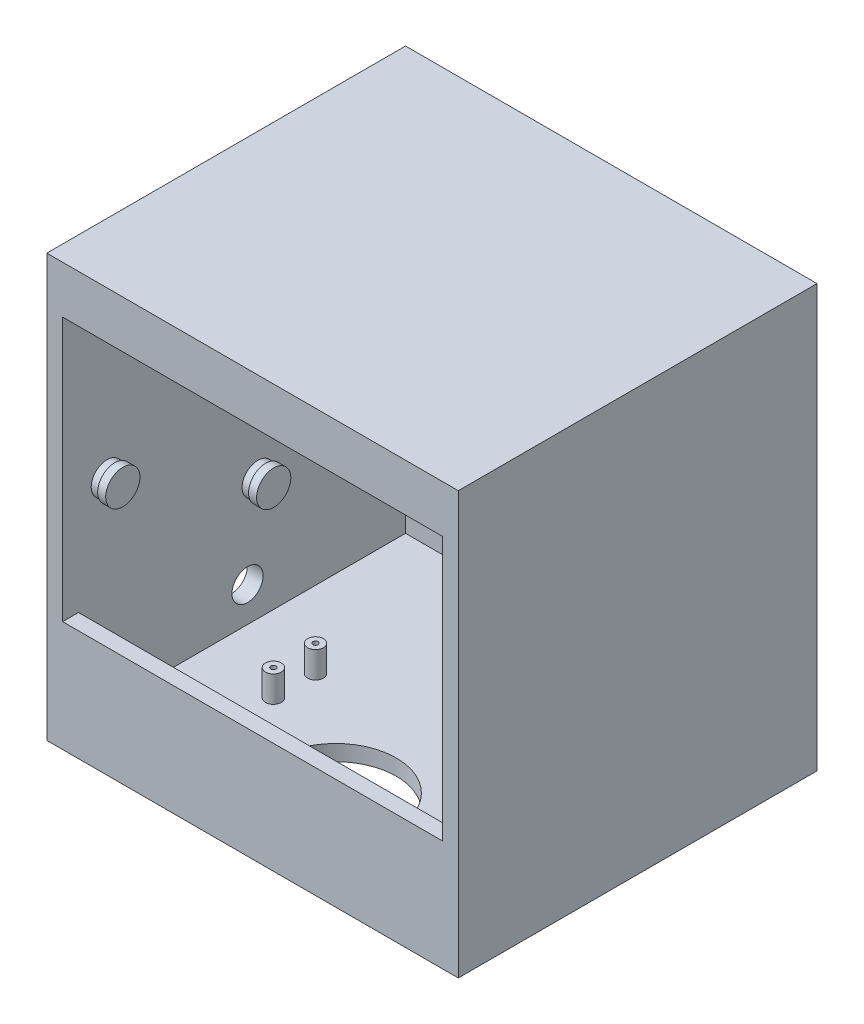
SolidWorks part; units mm, degrees
ref_plane "Front Plane" through (0, 0, 0) normal (0, 0, 1) x (1, 0, 0)
ref_plane "Top Plane" through (0, 0, 0) normal (0, 1, 0) x (1, 0, 0)
ref_plane "Right Plane" through (0, 0, 0) normal (1, 0, 0) x (0, 0, -1)
sketch "Base Plate Sketch" plane through (0, 0, 0) normal (0, 1, 0) x (1, 0, 0)
  line L1 (-176.9042, 232.645) -> (280.2958, 232.645)
  line L2 (-176.9042, 232.645) -> (-176.9042, -161.055)
  line L3 (-176.9042, -161.055) -> (280.2958, -161.055)
  line L4 (280.2958, 232.645) -> (280.2958, -161.055)
  line L5 (-195.9542, 251.695) -> (299.3458, 251.695)
  line L6 (-195.9542, 251.695) -> (-195.9542, -180.105)
  line L7 (-195.9542, -180.105) -> (299.3458, -180.105)
  line L8 (299.3458, 251.695) -> (299.3458, -180.105)
  line L9 (51.6958, 232.645) -> (51.6958, -161.055)
  circle A0 centre (51.6958, -80.0925) radius 73.025
  circle A1 centre (-72.1292, -80.755) radius 4.1
  circle A2 centre (-72.1292, 203.67) radius 4.1
  circle A3 centre (-84.8292, 32.22) radius 9.5
  circle A4 centre (-84.8292, -18.5299) radius 9.5
  circle A5 centre (-84.8292, 32.22) radius 3.175
  circle A6 centre (-84.8292, -18.5299) radius 3.175
  circle A7 centre (175.5208, -80.755) radius 4.1
  circle A8 centre (188.2208, -18.5299) radius 3.175
  circle A9 centre (188.2208, -18.5299) radius 9.5
  circle A10 centre (188.2208, 32.22) radius 3.175
  circle A11 centre (188.2208, 32.22) radius 9.5
  circle A12 centre (175.5208, 203.67) radius 4.1
  dimension "D7" = 146.05
  dimension "D9" = 8.2
  dimension "D10" = 12.7
  dimension "D11" = 80.3
  dimension "D12" = 8.2
  dimension "D13" = 284.425
  dimension "D14" = 19
  dimension "D15" = 19
  dimension "D19" = 6.35
  dimension "D20" = 6.35
  dimension "D1" = 393.7
  dimension "D2" = 457.2
  dimension "D3" = 19.05
  dimension "D4" = 19.05
  dimension "D5" = 19.05
  dimension "D6" = 19.05
  dimension "D8" = 312.7375
  dimension "D16" = 50.75
  dimension "D17" = 123.825
  dimension "D21" = 28.975
  dimension "D22" = 171.45
extrude "Boss-Extrude2" add sketch "Base Plate Sketch" along normal blind 31.75 contours A10 | A11 | A8 | A9 | A5 | A3 | A6 | A4
extrude "Boss-Extrude3" add sketch "Sketch1<5>" against normal blind 19.05 contours L5 L8 L7 L6
sketch "Sketch1<5>" plane through (0, 0, 0) normal (0, 1, 0) x (1, 0, 0) same geometry as "Base Plate Sketch"
extrude "Cut-Extrude1" cut sketch "Sketch1<6>" against normal blind 99.05 contours A2 | A1 | A0 | A7 | A12
sketch "Sketch1<6>" plane through (0, 0, 0) normal (0, 1, 0) x (1, 0, 0) same geometry as "Base Plate Sketch"
extrude "Boss-Extrude4" add sketch "Sketch1<7>" along normal blind 469.9 contours L6 L7 L8 L5 | L2 L3 L4 L1
sketch "Sketch1<7>" plane through (0, 0, 0) normal (0, 1, 0) x (1, 0, 0) same geometry as "Base Plate Sketch"
ref_plane "Plane1" through (-176.9042, 0, -232.645) normal (1, 0, 0) x (0, 0, -1)
sketch "Back Wall Sketch" plane through (0, 0, -232.645) normal (0, 0, 1) x (1, 0, 0)
  line L0 (-176.9042, 114.3) -> (280.2958, 114.3)
  line L1 (-176.9042, 469.9) -> (-176.9042, 0) construction
  line L2 (280.2958, 469.9) -> (280.2958, 0) construction
  line L3 (-176.9042, 266.7) -> (280.2958, 266.7)
  line L4 (-176.9042, 0) -> (280.2958, 0) construction
  line L5 (-176.9042, 469.9) -> (280.2958, 469.9) construction
  line L6 (51.6958, 266.7) -> (51.6958, 469.9)
  line L7 (280.2958, 266.7) -> (280.2958, 114.3)
  line L8 (-176.9042, 266.7) -> (-176.9042, 114.3)
  circle A0 centre (-117.9716, 342.325) radius 1.875
  circle A2 centre (-21.0417, 294.9875) radius 1.875
  circle A4 centre (-117.9716, 316.575) radius 1.875
  circle A5 centre (124.4333, 294.9875) radius 1.875
  circle A6 centre (221.3633, 342.325) radius 1.875
  circle A7 centre (221.3633, 316.575) radius 1.875
  circle A8 centre (184.1213, 148.3) radius 16.8
  dimension "D3" = 3.75
  dimension "D4" = 3.75
  dimension "D5" = 3.75
  dimension "D10" = 33.6
  dimension "D1" = 114.3
  dimension "D2" = 152.4
  dimension "D6" = 127.575
  dimension "D7" = 25.75
  dimension "D8" = 174.9125
  dimension "D9" = 155.8625
  dimension "D11" = 96.1746
  dimension "D12" = 118.4
extrude "Boss-Extrude5" add sketch "Back Wall Sketch" against normal blind 38.3 contours L8 L0 L7 L3
extrude "Cut-Extrude2" cut sketch "Back Wall Sketch<5>" against normal blind 19.25 contours L3 L7 L0 L8
sketch "Back Wall Sketch<5>" plane through (0, 0, -232.645) normal (0, 0, 1) x (1, 0, 0) same geometry as "Back Wall Sketch"
extrude "Cut-Extrude5" cut sketch "Back Wall Sketch<7>" against normal blind 28.875 contours A8
sketch "Back Wall Sketch<7>" plane through (0, 0, -232.645) normal (0, 0, 1) x (1, 0, 0) same geometry as "Back Wall Sketch"
extrude "Cut-Extrude6" cut sketch "Back Wall Sketch<8>" against normal blind 28.875 contours A2 | A4 | A0 | A6 | A7 | A5
sketch "Back Wall Sketch<8>" plane through (0, 0, -232.645) normal (0, 0, 1) x (1, 0, 0) same geometry as "Back Wall Sketch"
sketch "Left Wall Sketch" plane through (-176.9042, 0, 0) normal (1, 0, 0) x (0, 0, -1)
  line L0 (232.645, 0) -> (-161.055, 0) construction
  line L1 (251.695, 266.7) -> (251.695, 114.3) construction
  line L2 (232.645, 114.3) -> (232.645, 0) construction
  circle A0 centre (-126.7142, 237.44) radius 19
  circle A1 centre (54.8951, 146) radius 19
  circle A2 centre (42.445, 41.61) radius 18.75
  dimension "D1" = 38
  dimension "D2" = 38
  dimension "D3" = 37.5
  dimension "D5" = 146
  dimension "D9" = 41.61
  dimension "D4" = 237.44
  dimension "D6" = 378.4092
  dimension "D7" = 196.8
  dimension "D8" = 190.2
extrude "Cut-Extrude7" cut sketch "Left Wall Sketch" against normal blind 28.875 contours A2
extrude "Boss-Extrude6" add sketch "Left Wall Sketch<3>" along normal blind 9.35 contours A1 | A0
sketch "Left Wall Sketch<3>" plane through (-176.9042, 0, 0) normal (1, 0, 0) x (0, 0, -1) same geometry as "Left Wall Sketch"
sketch "Sketch5" plane through (-167.5542, 0, 0) normal (1, 0, 0) x (0, 0, -1)
  circle A0 centre (-126.7142, 237.44) radius 20.6
  circle A1 centre (54.8951, 146) radius 20.6
  dimension "D1" = 41.2
  dimension "D2" = 41.2
extrude "Boss-Extrude7" add sketch "Sketch5" along normal blind 9.7
sketch "Chamber Door Sketch" plane through (0, 0, 161.055) normal (0, 0, -1) x (-1, 0, 0)
  line L0 (-280.2958, 431.8) -> (176.9042, 431.8)
  line L1 (-280.2958, 469.9) -> (-280.2958, 0) construction
  line L2 (176.9042, 469.9) -> (176.9042, 0) construction
  line L3 (-280.2958, 114.3) -> (176.9042, 114.3)
  line L4 (176.9042, 0) -> (-280.2958, 0) construction
  line L5 (176.9042, 469.9) -> (-280.2958, 469.9) construction
  line L6 (-280.2958, 431.8) -> (-280.2958, 114.3)
  line L7 (176.9042, 431.8) -> (176.9042, 114.3)
  dimension "D1" = 114.3
  dimension "D2" = 38.1
extrude "Cut-Extrude8" cut sketch "Chamber Door Sketch" against normal blind 25.4 contours L0 L7 L3 L6
sketch "Top Sketch" plane through (0, 469.9, 0) normal (0, 1, 0) x (1, 0, 0)
  line L1 (-195.9542, 251.695) -> (299.3458, 251.695)
  line L2 (-195.9542, 251.695) -> (-195.9542, -180.105)
  line L3 (-195.9542, -180.105) -> (299.3458, -180.105)
  line L4 (299.3458, 251.695) -> (299.3458, -180.105)
extrude "Boss-Extrude8" add sketch "Top Sketch" along normal blind 19.05 contours L4 L3 L2 L1
sketch "Sketch7" plane through (0, 469.9, 0) normal (0, -1, 0) x (1, 0, 0)
  line L0 (-176.9042, -232.645) -> (280.2958, -232.645) construction
  line L1 (22.0201, -181.825) -> (11.0101, -162.755)
  line L2 (11.0101, -162.755) -> (-11.0101, -162.755)
  line L3 (-11.0101, -162.755) -> (-22.0201, -181.825)
  line L4 (-22.0201, -181.825) -> (-11.0101, -200.895)
  line L5 (-11.0101, -200.895) -> (11.0101, -200.895)
  line L6 (11.0101, -200.895) -> (22.0201, -181.825)
  circle A0 centre (0, -181.825) radius 19.07 construction
  point P1 (0, -200.895)
  dimension "D1" = 38.14
  dimension "D2" = 31.75
extrude "Boss-Extrude9" add sketch "Sketch7" along normal blind 12.7 contours L2 L3 L4 L5 L6 L1
